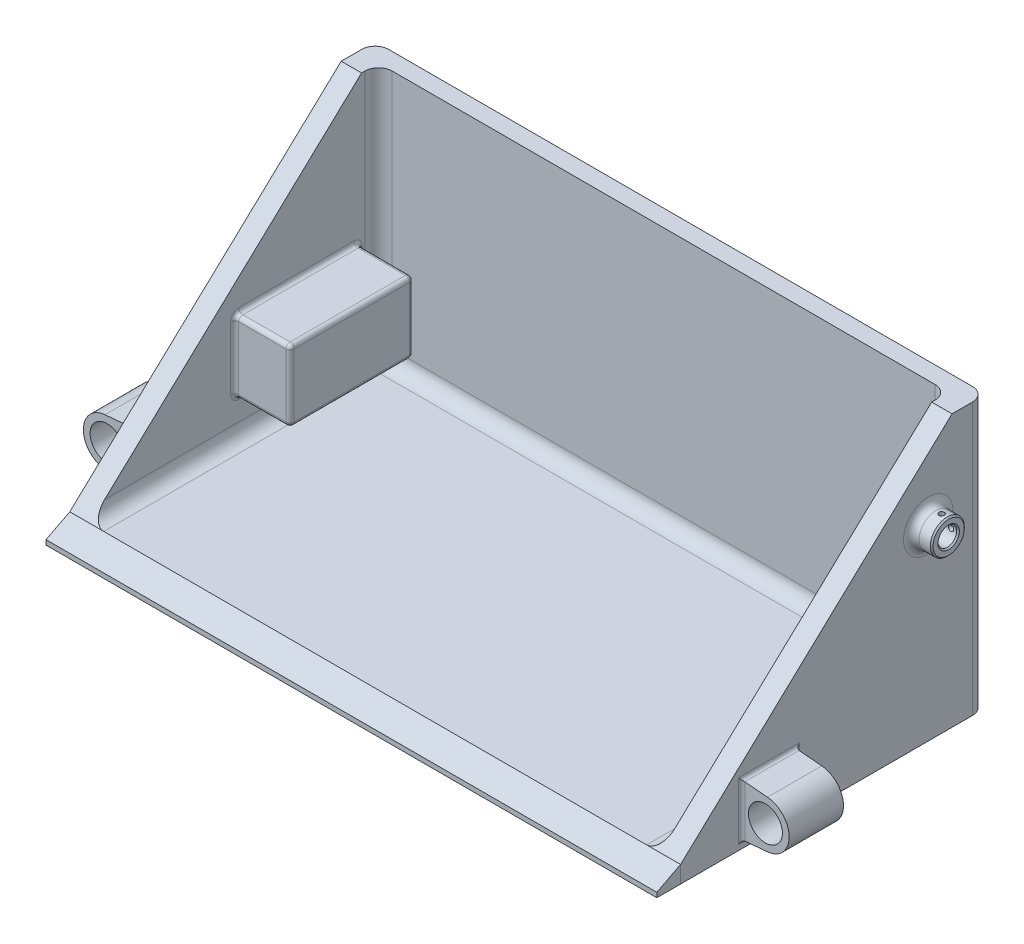
SolidWorks part; units mm, degrees
ref_plane "Front Plane" through (0, 0, 0) normal (0, 0, 1) x (1, 0, 0)
ref_plane "Top Plane" through (0, 0, 0) normal (0, 1, 0) x (1, 0, 0)
ref_plane "Right Plane" through (0, 0, 0) normal (1, 0, 0) x (0, 0, -1)
sketch "Sketch1" plane through (0, 0, 0) normal (0, 1, 0) x (1, 0, 0)
  line L1 (-114.3, 57.15) -> (114.3, 57.15)
  line L2 (-114.3, 57.15) -> (-114.3, -57.15)
  line L3 (-114.3, -57.15) -> (114.3, -57.15)
  line L4 (114.3, 57.15) -> (114.3, -57.15)
  line L5 (-114.3, 57.15) -> (114.3, -57.15) construction
  line L6 (-114.3, -57.15) -> (114.3, 57.15) construction
  point P0 (0, 0)
  dimension "D1" = 228.6
  dimension "D2" = 114.3
extrude "Boss-Extrude1" add sketch "Sketch1" along normal mid plane 6.35
sketch "Sketch3" plane through (-114.3, 0, 0) normal (-1, 0, 0) x (0, 0, 1)
  line L0 (-57.15, 3.175) -> (-57.15, 98.425)
  line L1 (-57.15, 98.425) -> (-44.45, 98.425)
  line L2 (-44.45, 98.425) -> (57.15, 3.175)
  line L3 (57.15, 3.175) -> (-57.15, 3.175)
  line L4 (-57.15, -3.175) -> (57.15, -3.175) construction
  dimension "D1" = 101.6
  dimension "D2" = 12.7
extrude "Boss-Extrude2" add sketch "Sketch3" against normal blind 7.62
mirror "Mirror1" about plane through (0, 0, 0) normal (1, 0, 0) of "Boss-Extrude2"
sketch "Sketch4" plane through (0, 3.175, 0) normal (0, 1, 0) x (1, 0, 0)
  line L0 (-106.68, 57.15) -> (106.68, 57.15)
  line L1 (106.68, 57.15) -> (106.68, 50.8)
  line L2 (106.68, 50.8) -> (-106.68, 50.8)
  line L3 (-106.68, 50.8) -> (-106.68, 57.15)
  dimension "D1" = 6.35
extrude "Boss-Extrude3" add sketch "Sketch4" along normal up to surface (95.25 mm away) up to face at (-110.49, 98.425, -50.8)
sketch "Sketch5" plane through (-114.3, 0, 0) normal (-1, 0, 0) x (0, 0, 1)
  line L1 (66.04, -3.175) -> (57.15, -3.175)
  line L2 (57.15, -3.175) -> (57.15, 3.175)
  line L3 (-57.15, 98.425) -> (-57.15, -3.175) construction
  line L4 (57.15, 3.175) -> (66.04, -1.397)
  line L5 (66.04, -1.397) -> (66.04, -3.175)
  dimension "D1" = 123.19
  dimension "D2" = 1.778
extrude "Boss-Extrude4" add sketch "Sketch5" along direction (1, 0, 0) on the side against the normal up to surface (228.6 mm away) separate body up to face at (114.3, 38.735, -8.89)
fillet "Fillet2" radius 5.08 5 edges at (106.68, 3.175, 3.175) (106.68, 50.8, -50.8) (0, 3.175, -50.8) (-106.68, 3.175, 3.175) (-106.68, 50.8, -50.8)
fillet "Fillet3" radius 5.08 2 edges at (114.3, 47.625, -57.15) (-114.3, 47.625, -57.15)
sketch "Sketch6" plane through (114.3, 0, 0) normal (1, 0, 0) x (0, 0, -1)
  line L0 (-57.15, -3.175) -> (52.07, -3.175) construction
  line L1 (57.15, 98.425) -> (57.15, -3.175) construction
  circle A0 centre (35.56, 66.675) radius 3.4925
  circle A1 centre (35.56, 66.675) radius 6.35
  dimension "D1" = 6.985
  dimension "D2" = 12.7
  dimension "D3" = 69.85
  dimension "D4" = 21.59
extrude "Boss-Extrude5" add sketch "Sketch6" along normal blind 7.62
mirror "Mirror2" about plane through (0, 0, 0) normal (1, 0, 0) of "Boss-Extrude5"
fillet "Fillet4" radius 2.921 2 edges at (114.3, 66.675, -29.21) (-114.3, 66.675, -41.91)
chamfer "Chamfer1" distance 0.508 angle 45 4 edges at (121.92, 66.675, -39.0525) (121.92, 66.675, -41.91) (-121.92, 66.675, -39.0525) (-121.92, 66.675, -41.91)
ref_plane "setscrew_lhs_plane" through (0, 73.025, 0) normal (0, 1, 0) x (1, 0, 0)
sketch "Sketch7" plane through (0, 73.025, 0) normal (0, 1, 0) x (1, 0, 0)
  line L0 (117.221, 29.21) -> (121.412, 29.21) construction
  line L1 (121.412, 41.91) -> (117.221, 41.91) construction
  line L2 (117.221, 29.21) -> (121.412, 29.21) construction
  line L3 (121.412, 41.91) -> (117.221, 41.91) construction
  line L4 (119.3165, 41.91) -> (119.3165, 29.21) construction
  circle A0 centre (119.3165, 35.56) radius 1.0033
  dimension "D1" = 2.0066
extrude "Cut-Extrude1" cut sketch "Sketch7" against normal blind 3.81
pattern_circular "CirPattern1" count 2 every 90 about axis through (121.92, 66.675, -35.56) along (-1, 0, 0) of "Cut-Extrude1"
mirror "Mirror3" about plane through (0, 0, 0) normal (1, 0, 0) of "CirPattern1"
sketch "Sketch8" plane through (-114.3, 0, 0) normal (-1, 0, 0) x (0, 0, 1)
  line L0 (-57.15, -3.175) -> (-57.15, 98.425) construction
  line L1 (-40.64, 41.275) -> (0.508, 41.275)
  line L2 (-40.64, 41.275) -> (-40.64, 19.685)
  line L3 (-40.64, 19.685) -> (0.508, 19.685)
  line L4 (0.508, 41.275) -> (0.508, 19.685)
  line L5 (-40.64, 41.275) -> (0.508, 19.685) construction
  line L6 (-40.64, 19.685) -> (0.508, 41.275) construction
  line L7 (-52.07, -3.175) -> (57.15, -3.175) construction
  point P0 (-20.066, 30.48)
  dimension "D1" = 16.51
  dimension "D2" = 41.148
  dimension "D3" = 22.86
  dimension "D4" = 21.59
extrude "Cut-Extrude2" cut sketch "Sketch8" against normal up to surface (7.62 mm away) up to face at (-106.68, 53.34, -21.0397)
sketch "Sketch9" plane through (-106.68, 0, 0) normal (1, 0, 0) x (0, 0, -1)
  line L0 (40.64, 41.275) -> (40.64, 19.685) construction
  line L1 (-0.508, 19.685) -> (-0.508, 41.275) construction
  line L2 (-0.508, 41.275) -> (40.64, 41.275) construction
  line L3 (40.64, 19.685) -> (-0.508, 19.685) construction
  line L4 (40.64, 41.275) -> (40.64, 19.685)
  line L5 (-0.508, 19.685) -> (-0.508, 41.275)
  line L6 (-0.508, 41.275) -> (40.64, 41.275)
  line L7 (40.64, 19.685) -> (-0.508, 19.685)
  line L8 (40.64, 30.48) -> (-0.508, 30.48) construction
  line L9 (20.066, 41.275) -> (20.066, 19.685) construction
  line L11 (-3.048, 17.145) -> (43.18, 17.145)
  line L12 (-3.048, 17.145) -> (-3.048, 43.815)
  line L13 (-3.048, 43.815) -> (43.18, 43.815)
  line L14 (43.18, 17.145) -> (43.18, 43.815)
  line L15 (-3.048, 17.145) -> (43.18, 43.815) construction
  line L16 (-3.048, 43.815) -> (43.18, 17.145) construction
  point P8 (20.066, 30.48)
  dimension "D1" = 2.54
  dimension "D2" = 2.54
extrude "Boss-Extrude6" add sketch "Sketch9" along normal blind 17.78
sketch "Sketch10" plane through (-88.9, 0, 0) normal (1, 0, 0) x (0, 0, -1)
  line L4 (43.18, 17.145) -> (43.18, 43.815)
  line L5 (43.18, 43.815) -> (-3.048, 43.815)
  line L6 (-3.048, 43.815) -> (-3.048, 17.145)
  line L7 (-3.048, 17.145) -> (43.18, 17.145)
  line L8 (43.18, 17.145) -> (43.18, 43.815)
  line L9 (43.18, 43.815) -> (-3.048, 43.815)
  line L10 (-3.048, 43.815) -> (-3.048, 17.145)
  line L11 (-3.048, 17.145) -> (43.18, 17.145)
  dimension "D1" = 0
extrude "Boss-Extrude7" add sketch "Sketch10" along normal blind 2.921
fillet "Fillet5" radius 1.524 12 edges at (-106.68, 30.48, 3.048) (-96.3295, 43.815, 3.048) (-106.68, 43.815, -20.066) (-85.979, 30.48, 3.048) (-85.979, 43.815, -20.066) (-85.979, 30.48, -43.18) (-96.3295, 43.815, -43.18) (-106.68, 30.48, -43.18) (-96.3295, 17.145, 3.048) (-85.979, 17.145, -20.066) (-96.3295, 17.145, -43.18) (-106.68, 17.145, -20.066)
fillet "Fillet6" radius 1.524 4 edges at (-101.6, 19.685, -40.64) (-101.6, 19.685, 0.508) (-101.6, 41.275, 0.508) (-101.6, 41.275, -40.64)
sketch "Sketch11" plane through (-114.3, 0, 0) normal (-1, 0, 0) x (0, 0, 1)
  line L0 (-20.066, 41.275) -> (-20.066, 19.685) construction
  line L1 (-39.116, 41.275) -> (-1.016, 41.275) construction
  line L2 (-1.016, 19.685) -> (-39.116, 19.685) construction
  line L3 (0.508, 30.48) -> (-40.64, 30.48) construction
  line L4 (0.508, 39.751) -> (0.508, 21.209) construction
  line L5 (-40.64, 21.209) -> (-40.64, 39.751) construction
  line L11 (-45.085, 35.56) -> (4.953, 35.56) construction
  line L12 (-40.64, 39.751) -> (-40.64, 21.209) construction
  line L13 (-40.64, 38.735) -> (-40.64, 22.225)
  line L14 (-40.64, 38.735) -> (-48.26, 38.735)
  line L15 (-48.26, 38.735) -> (-48.26, 22.225)
  line L16 (-48.26, 22.225) -> (-40.64, 22.225)
  line L17 (0.508, 38.735) -> (8.128, 38.735)
  line L18 (8.128, 38.735) -> (8.128, 22.225)
  line L19 (0.508, 38.735) -> (0.508, 22.225)
  line L20 (8.128, 22.225) -> (0.508, 22.225)
  circle A2 centre (-45.085, 35.56) radius 1.524
  circle A3 centre (4.953, 35.56) radius 1.524
  circle A4 centre (4.953, 25.4) radius 1.524
  circle A5 centre (-45.085, 25.4) radius 1.524
  point P16 (-20.066, 35.56)
  point P23 (-40.64, 30.48)
  dimension "D2" = 3.048
  dimension "D3" = 3.048
  dimension "D4" = 50.038
  dimension "D5" = 10.16
  dimension "D1" = 16.51
  dimension "D6" = 7.62
extrude "Boss-Extrude8" add sketch "Sketch11" along normal blind 3.81
ref_plane "Plane1" through (0, 0, -20.066) normal (0, 0, 1) x (1, 0, 0)
ref_plane "Plane2" through (0, 30.48, 0) normal (0, -1, 0) x (-1, 0, 0)
fillet "Fillet7" radius 1.27 6 edges at (-114.3, 22.225, 4.318) (-114.3, 30.48, 8.128) (-114.3, 38.735, 4.318) (-114.3, 22.225, -44.45) (-114.3, 30.48, -48.26) (-114.3, 38.735, -44.45)
ref_plane "Plane3" through (0, 0, 24.13) normal (0, 0, -1) x (-1, 0, 0)
ref_plane "Plane4" through (0, 0, -6.35) normal (0, 0, -1) x (-1, 0, 0)
sketch "Sketch12" plane through (0, 0, 24.13) normal (0, 0, -1) x (-1, 0, 0)
  line L0 (114.3, 98.425) -> (114.3, -3.175) construction
  line L1 (-109.22, -3.175) -> (109.22, -3.175) construction
  line L2 (123.9648, 18.3812) -> (114.3, 19.2267)
  line L3 (123.9648, 0.6688) -> (114.3, -0.1767)
  line L4 (123.19, 9.525) -> (114.3, 9.525) construction
  line L5 (114.3, 19.2267) -> (114.3, -0.1767)
  circle A0 centre (123.19, 9.525) radius 6.35
  arc A1 (123.9648, 0.6688) -> (123.9648, 18.3812) centre (123.19, 9.525) ccw
  dimension "D1" = 12.7
  dimension "D2" = 17.78
  dimension "D5" = 5
  dimension "D3" = 8.89
  dimension "D4" = 12.7
  dimension "D6" = 5
extrude "Boss-Extrude9" add sketch "Sketch12" along normal mid plane 20.32
mirror "Mirror4" about plane through (0, 0, 0) normal (1, 0, 0) of "Boss-Extrude9"
fillet "Fillet8" radius 1.27 8 edges at (-114.3, -0.1767, 24.13) (-114.3, 9.525, 13.97) (-114.3, 9.525, 34.29) (-114.3, 19.2267, 24.13) (114.3, 19.2267, 24.13) (114.3, 9.525, 13.97) (114.3, -0.1767, 24.13) (114.3, 9.525, 34.29)
equation "\"D3@Sketch11\"=\"D2@Sketch11\""
